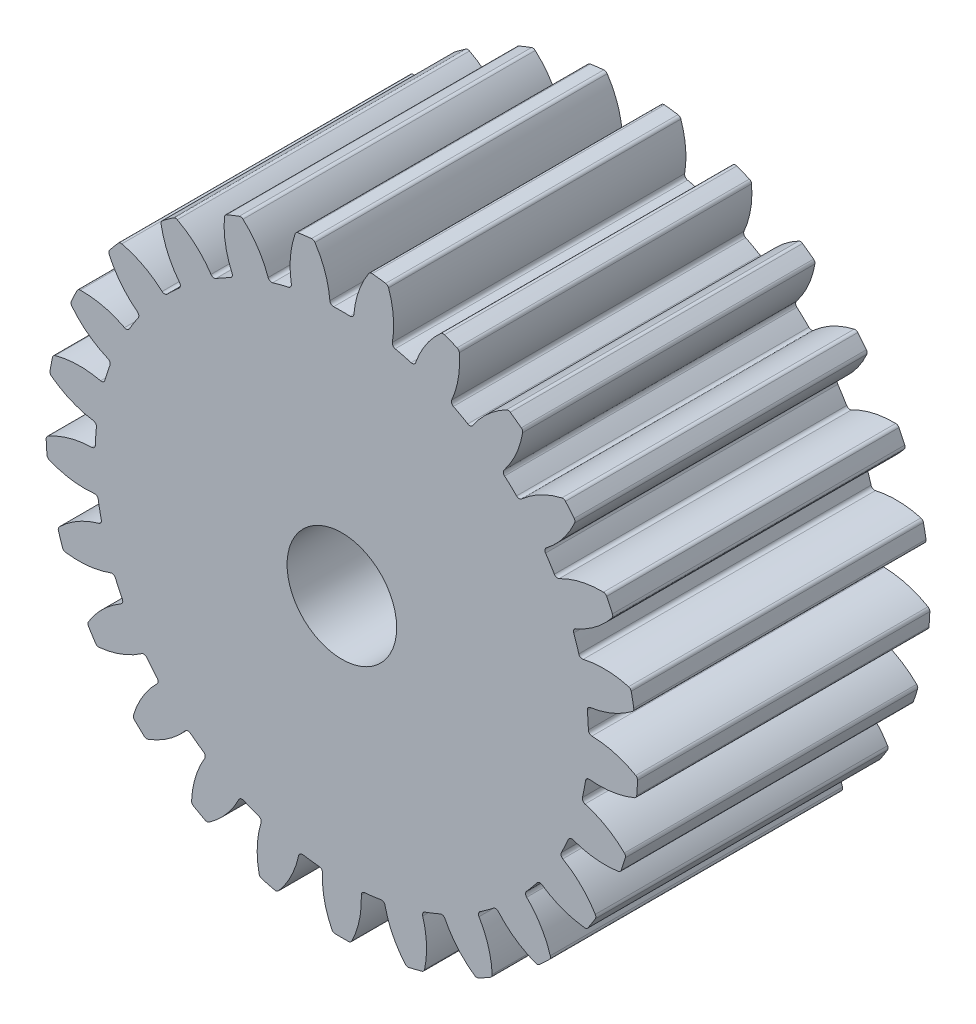
SolidWorks part; units mm, degrees
material "Нержавеющая сталь (ферритная)"
ref_plane "Спереди" through (0, 0, 0) normal (0, 0, 1) x (1, 0, 0)
ref_plane "Сверху" through (0, 0, 0) normal (0, 1, 0) x (1, 0, 0)
ref_plane "Справа" through (0, 0, 0) normal (1, 0, 0) x (0, 0, -1)
sketch "Эскиз1" plane through (0, 0, 0) normal (0, 0, 1) x (1, 0, 0)
  circle A0 centre (0, 0) radius 8.1
  circle A1 centre (0, 0) radius 1.5
  dimension "D1" = 16.2
  dimension "D2" = 3
extrude "Бобышка-Вытянуть1" add sketch "Эскиз1" along normal mid plane 8
sketch "Эскиз2" plane through (0, 0, 0) normal (0, 0, 1) x (1, 0, 0)
  line L0 (0, 0) -> (0, 8.1) construction
  line L1 (-0.3216, 6.7423) -> (0, 0) construction
  line L2 (-0.4709, 7.4852) -> (0, 6.1913) construction
  line L3 (-0.4709, 7.4852) -> (0.4709, 7.4852) construction
  line L4 (0.4709, 7.4852) -> (1.4054, 7.3672) construction
  line L5 (0, 0) -> (0.9381, 7.4262) construction
  arc A0 (1.4054, 7.3672) -> (-0.4709, 7.4852) centre (0, 0) ccw construction
  arc A1 (0.3216, 6.7423) -> (-0.3216, 6.7423) centre (0, 0) ccw
  circle A2 centre (0, 0) radius 8.1 construction
  arc A3 (0.7707, 8.0632) -> (-0.7707, 8.0632) centre (0, 0) ccw
  arc A4 (0.3216, 6.7423) -> (0.7707, 8.0632) centre (2.8423, 6.6221) cw
  arc A5 (-0.3216, 6.7423) -> (-0.7707, 8.0632) centre (-2.8423, 6.6221) ccw
  dimension "D1" = 13.5
  dimension "D2" = 15
  dimension "D3" = 20
  dimension "D4" = 7.2
extrude "Вырез-Вытянуть1" cut sketch "Эскиз2" against normal through all both and the other way through all
fillet "Скругление1" radius 0.1 4 edges at (0.7707, 8.0632, 0) (0.3216, 6.7423, 0) (-0.3216, 6.7423, 0) (-0.7707, 8.0632, 0)
pattern_circular "Круговой массив1" count 25 over 360 about axis through (0, 0, 4) along (0, 0, -1) of "Вырез-Вытянуть1", "Скругление1"
